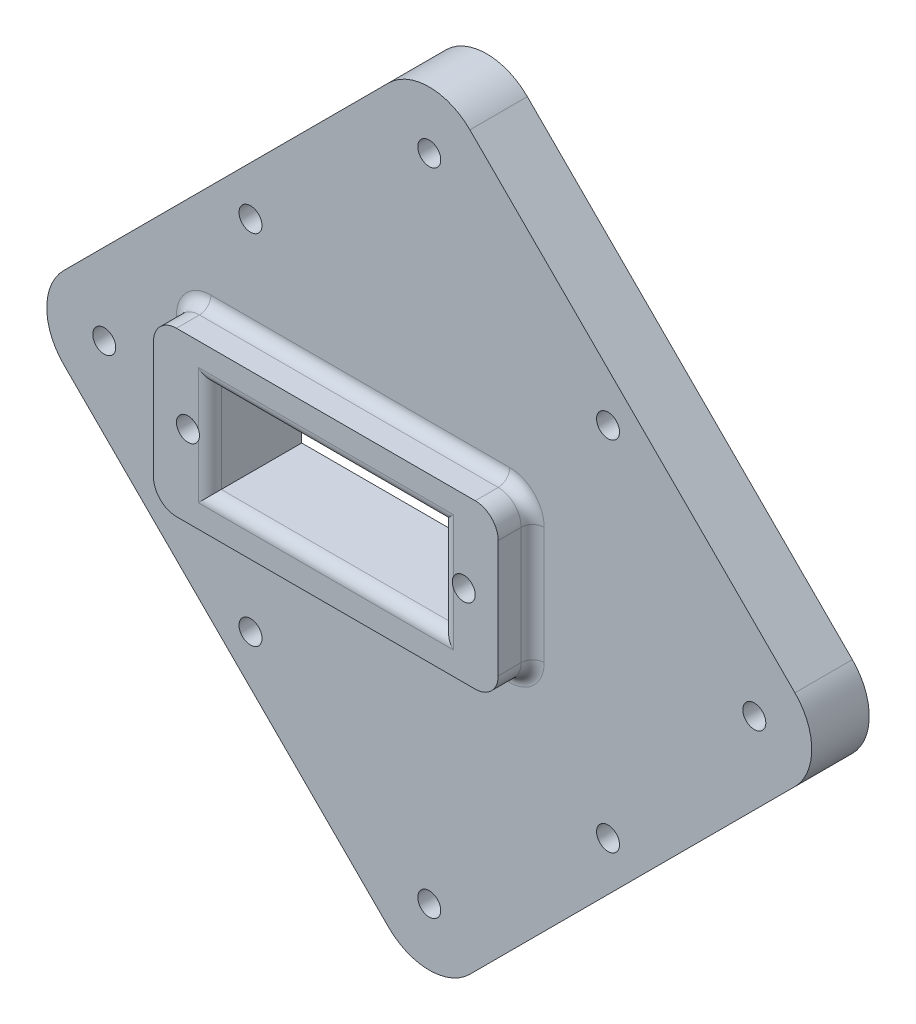
SolidWorks part; units mm, degrees
ref_plane "Front Plane" through (0, 0, 0) normal (0, 0, 1) x (1, 0, 0)
ref_plane "Top Plane" through (0, 0, 0) normal (0, 1, 0) x (1, 0, 0)
ref_plane "Right Plane" through (0, 0, 0) normal (1, 0, 0) x (0, 0, -1)
sketch "Sketch1" plane through (0, 0, 0) normal (0, 0, 1) x (1, 0, 0)
  line L0 (0, 0) -> (0, 60)
  line L1 (0, -55) -> (0, 55) construction
  line L2 (0, 60) -> (60, 60)
  line L3 (60, 60) -> (60, 0)
  line L4 (55, 0) -> (-55, 0) construction
  line L5 (60, 0) -> (0, 0)
extrude "Boss-Extrude1" add sketch "Sketch1" along normal blind 5
sketch "Sketch2" plane through (0, 0, 5) normal (0, 0, 1) x (1, 0, 0)
  line L0 (0, 60) -> (60, 0) construction
  line L1 (2.75, 0) -> (-2.75, 0) construction
  line L2 (60, 0) -> (60, 60) construction
  line L3 (0, 0) -> (60, 60) construction
  line L4 (30, 30) -> (34.1, 30) construction
  line L5 (34.1, 30) -> (34.1, 34.1) construction
  line L6 (34.1, 34.1) -> (13.9, 34.1)
  line L7 (13.9, 34.1) -> (13.9, 25.9)
  line L8 (13.9, 25.9) -> (34.1, 25.9)
  line L9 (34.1, 25.9) -> (34.1, 34.1)
  line L11 (9, 37.1) -> (39, 37.1)
  line L12 (39, 37.1) -> (39, 22.9)
  line L13 (9, 37.1) -> (9, 22.9)
  line L14 (9, 22.9) -> (39, 22.9)
  point P24 (39, 30)
  point P25 (9, 30)
extrude "Boss-Extrude2" add sketch "Sketch2" along normal blind 3
sketch "Sketch3" plane through (0, 0, 5) normal (0, 0, 1) x (1, 0, 0)
  line L1 (13.9, 34.1) -> (34.1, 34.1)
  line L2 (13.9, 34.1) -> (13.9, 25.9)
  line L3 (13.9, 25.9) -> (34.1, 25.9)
  line L4 (34.1, 34.1) -> (34.1, 25.9)
extrude "Cut-Extrude1" cut sketch "Sketch3" against normal blind 15
sketch "Sketch4" plane through (0, 0, 0) normal (0, 0, -1) x (-1, 0, 0)
  line L0 (-60, 60) -> (0, 0) construction
  line L1 (0, 60) -> (-60, 0) construction
  line L2 (0, 4.4) -> (0, -4.4) construction
  line L3 (-60, 60) -> (0, 60) construction
ref_point "Point1"
ref_axis "Axis1" through (30, 30, 39.6129) along (0, 0, -1)
sketch "Sketch5" plane through (0, 0, 8) normal (0, 0, 1) x (1, 0, 0)
  line L0 (24, 30) -> (12, 30) construction
  line L1 (34.1, 34.1) -> (13.9, 25.9) construction
  line L2 (13.9, 34.1) -> (34.1, 25.9) construction
  line L3 (24, 30) -> (36, 30) construction
  circle A0 centre (12, 30) radius 1
  circle A1 centre (36, 30) radius 1
extrude "Cut-Extrude2" cut sketch "Sketch5" against normal blind 15
fillet "Fillet1" radius 2 8 edges at (60, 0, 2.5) (0, 0, 2.5) (0, 60, 2.5) (60, 60, 2.5) (9, 22.9, 6.5) (9, 37.1, 6.5) (39, 22.9, 6.5) (39, 37.1, 6.5)
sketch "Sketch6" plane through (0, 0, 0) normal (0, 0, -1) x (-1, 0, 0)
  line L2 (0, 60) -> (-60, 0) construction
  line L3 (-8.7868, 51.2132) -> (12.4264, 30)
  line L4 (12.4264, 30) -> (-30, -12.4264)
  line L5 (-30, -12.4264) -> (-72.4264, 30)
  line L6 (-72.4264, 30) -> (-30, 72.4264)
  line L7 (-30, 72.4264) -> (-8.7868, 51.2132)
  line L8 (-91.699, 82.3667) -> (28.3183, 82.3667)
  line L9 (-91.699, 82.3667) -> (-91.699, -19.0564)
  line L10 (-91.699, -19.0564) -> (28.3183, -19.0564)
  line L11 (28.3183, 82.3667) -> (28.3183, -19.0564)
extrude "Cut-Extrude3" cut sketch "Sketch6" against normal blind 15
sketch "Sketch7" plane through (0, 0, 0) normal (0, 0, -1) x (-1, 0, 0)
  line L0 (-19.3934, 40.6066) -> (-8.7868, 30)
  line L2 (0, 42.4264) -> (-17.5736, 60) construction
  line L3 (-8.7868, 51.2132) -> (12.4264, 30)
  line L4 (12.4264, 30) -> (-30, -12.4264)
  line L5 (-30, -12.4264) -> (-72.4264, 30)
  line L6 (-72.4264, 30) -> (-30, 72.4264)
  line L7 (-30, 72.4264) -> (-8.7868, 51.2132)
  line L8 (-8.7868, 30) -> (-30, 8.7868)
  line L9 (-30, 8.7868) -> (-51.2132, 30)
  line L10 (-51.2132, 30) -> (-30, 51.2132)
  line L11 (-30, 51.2132) -> (-19.3934, 40.6066)
  dimension "D1" = 15
extrude "Boss-Extrude3" add sketch "Sketch7" against normal up to surface (5 mm away) up to face at (24, 30, 5)
sketch "Sketch8" plane through (0, 0, 0) normal (0, 0, -1) x (-1, 0, 0)
  line L14 (-30, -5.3553) -> (5.3553, 30)
  line L15 (-65.3553, 30) -> (-30, -5.3553)
  line L16 (5.3553, 30) -> (-30, 65.3553)
  line L17 (-30, 65.3553) -> (-65.3553, 30)
  line L18 (-30, -5.3553) -> (5.3553, 30)
  line L19 (-65.3553, 30) -> (-30, -5.3553)
  line L20 (5.3553, 30) -> (-30, 65.3553)
  line L21 (-30, 65.3553) -> (-65.3553, 30)
  line L32 (-30, -12.4264) -> (12.4264, 30)
  line L33 (-72.4264, 30) -> (-30, -12.4264)
  line L34 (-30, 72.4264) -> (-72.4264, 30)
  line L35 (12.4264, 30) -> (-30, 72.4264)
  line L36 (-30, -12.4264) -> (12.4264, 30)
  line L37 (-72.4264, 30) -> (-30, -12.4264)
  line L38 (-30, 72.4264) -> (-72.4264, 30)
  line L39 (12.4264, 30) -> (-30, 72.4264)
  dimension "D1" = 5
  dimension "D2" = 0
extrude "Cut-Extrude4" cut sketch "Sketch8" against normal blind 15
fillet "Fillet3" radius 5 4 edges at (30, -5.3553, 2.5) (65.3553, 30, 2.5) (30, 65.3553, 2.5) (-5.3553, 30, 2.5)
sketch "Sketch9" plane through (0, 0, 0) normal (0, 0, -1) x (-1, 0, 0)
  circle A0 centre (-30, 58.2843) radius 1
  circle A1 centre (-30, 1.7157) radius 1
  circle A2 centre (-1.7157, 30) radius 1
  circle A3 centre (-58.2843, 30) radius 1
extrude "Cut-Extrude5" cut sketch "Sketch9" against normal blind 15
sketch "Sketch10" plane through (0, 0, 0) normal (0, 0, -1) x (-1, 0, 0)
  line L0 (-47.6777, 47.6777) -> (-45.5563, 45.5563) construction
  line L1 (-33.5355, 61.8198) -> (-61.8198, 33.5355) construction
  line L2 (-60, 60) -> (0, 0) construction
  line L3 (-47.6777, 12.3223) -> (-45.5563, 14.4437) construction
  line L4 (-61.8198, 26.4645) -> (-33.5355, -1.8198) construction
  line L5 (0, 60) -> (-60, 0) construction
  line L6 (-12.3223, 12.3223) -> (-14.4437, 14.4437) construction
  line L7 (-26.4645, -1.8198) -> (1.8198, 26.4645) construction
  line L8 (-12.3223, 47.6777) -> (-14.4437, 45.5563) construction
  line L9 (1.8198, 33.5355) -> (-26.4645, 61.8198) construction
  circle A0 centre (-45.5563, 45.5563) radius 1
  circle A1 centre (-45.5563, 14.4437) radius 1
  circle A2 centre (-14.4437, 14.4437) radius 1
  circle A3 centre (-14.4437, 45.5563) radius 1
extrude "Cut-Extrude6" cut sketch "Sketch10" against normal blind 10
fillet "Fillet4" radius 1 12 edges at (38.4142, 36.5142, 5) (39, 30, 5) (38.4142, 23.4858, 5) (24, 22.9, 5) (9.5858, 23.4858, 5) (9, 30, 5) (9.5858, 36.5142, 5) (13.9, 30, 8) (24, 25.9, 8) (34.1, 30, 8) (24, 34.1, 8) (24, 37.1, 5)
